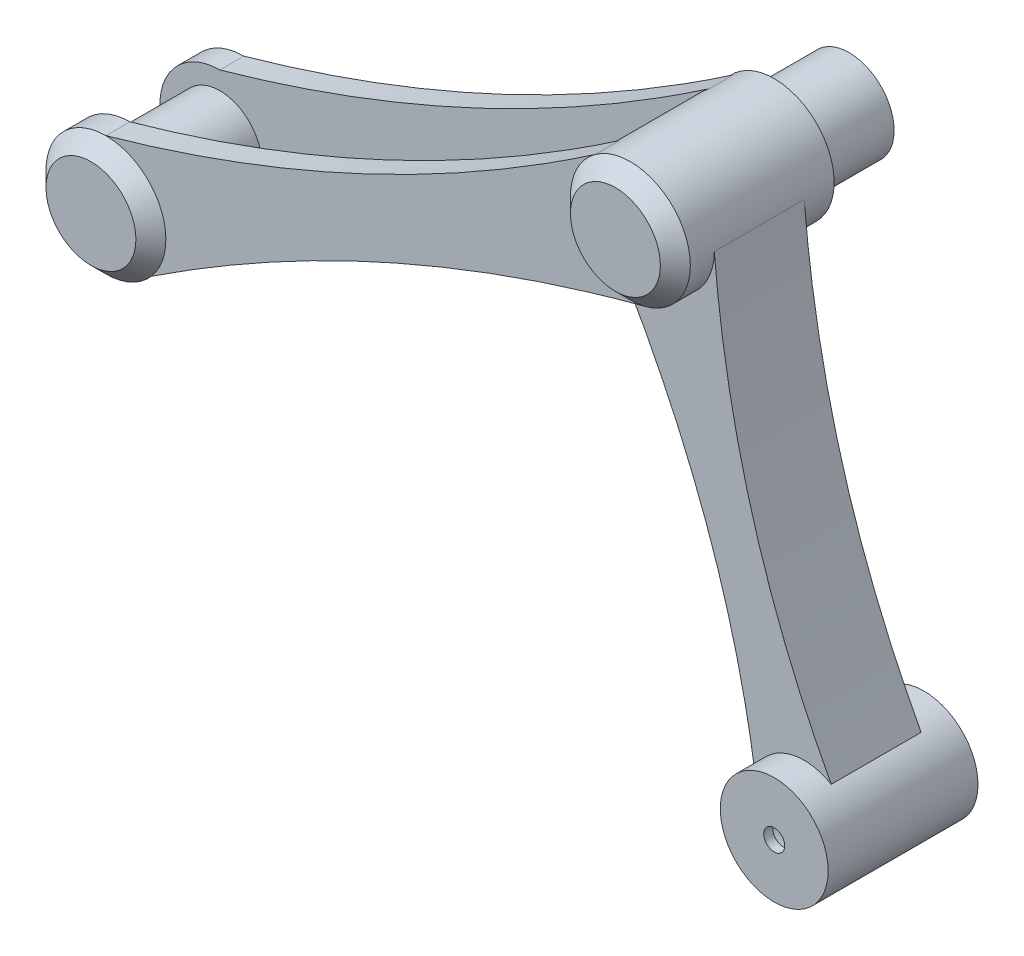
SolidWorks part; units mm, degrees
ref_plane "Front Plane" through (0, 0, 0) normal (0, 0, 1) x (1, 0, 0)
ref_plane "Top Plane" through (0, 0, 0) normal (0, 1, 0) x (1, 0, 0)
ref_plane "Right Plane" through (0, 0, 0) normal (1, 0, 0) x (0, 0, -1)
sketch "Sketch1" plane through (0, 0, 0) normal (0, 0, 1) x (1, 0, 0)
  circle A0 centre (0, 0) radius 14
extrude "Boss-Extrude1" add sketch "Sketch1" against normal blind 15 and the other way blind 15
sketch "Sketch2" plane through (0, 0, 0) normal (0, 0, 1) x (1, 0, 0)
  line L0 (0, 0) -> (175, 0) construction
  line L1 (175, 0) -> (175, 80) construction
  line L2 (175, 0) -> (225, 0) construction
  line L3 (225, 0) -> (225, -70) construction
sketch "Sketch3" plane through (0, 0, -15) normal (0, 0, -1) x (-1, 0, 0)
  circle A0 centre (0, 0) radius 20
extrude "Boss-Extrude2" add sketch "Sketch3" along normal blind 8
sketch "Sketch4" plane through (0, 0, 15) normal (0, 0, 1) x (1, 0, 0)
  circle A0 centre (0, 0) radius 20 construction
  circle A1 centre (0, 0) radius 20
extrude "Boss-Extrude3" add sketch "Sketch4" along normal blind 8
sketch "Sketch6" plane through (0, 0, 0) normal (0, 0, 1) x (1, 0, 0)
  circle A1 centre (175, 80) radius 15
extrude "Boss-Extrude5" add sketch "Sketch6" against normal blind 50 and the other way blind 15 separate body
sketch "Sketch7" plane through (0, 0, 15) normal (0, 0, 1) x (1, 0, 0)
  circle A0 centre (175, 80) radius 20
extrude "Boss-Extrude6" add sketch "Sketch7" along normal blind 10
sketch "Sketch8" plane through (0, 0, -50) normal (0, 0, -1) x (-1, 0, 0)
  line L0 (-182.5, 80) -> (-167.5, 80) construction
  circle A0 centre (-182.5, 80) radius 2
  circle A1 centre (-167.5, 80) radius 2
extrude "Cut-Extrude1" cut sketch "Sketch8" against normal blind 30
sketch "Sketch9" plane through (0, 0, 15) normal (0, 0, -1) x (-1, 0, 0)
  circle A0 centre (-175, 80) radius 15
  circle A1 centre (-175, 80) radius 20
extrude "Boss-Extrude7" add sketch "Sketch9" along normal blind 40
sketch "Sketch10" plane through (0, 0, 25) normal (0, 0, 1) x (1, 0, 0)
  line L0 (0, 0) -> (175, 80) construction
  line L1 (175, 80) -> (225, -70) construction
  circle A0 centre (0, 0) radius 20
  circle A1 centre (175, 80) radius 20
  circle A2 centre (225, -70) radius 18 construction
  circle A3 centre (225, -70) radius 12.8 construction
sketch "Sketch11" plane through (0, 0, 25) normal (0, 0, 1) x (1, 0, 0)
  circle A0 centre (225, -70) radius 18 construction
  circle A1 centre (225, -70) radius 18
  circle A2 centre (225, -70) radius 12.8 construction
  circle A3 centre (225, -70) radius 12.8
sketch "Sketch13" plane through (0, 0, 23) normal (0, 0, 1) x (1, 0, 0)
  line L0 (0, 0) -> (175, 80) construction
  line L1 (175, 80) -> (225, -70) construction
  circle A1 centre (175, 80) radius 20
  circle A2 centre (175, 80) radius 20
  circle A5 centre (0, 0) radius 20
  circle A6 centre (175, 80) radius 20
  spline S0 degree 2 poles (0, 20) (88.2168, 44.7305) (164.022, 96.7178) knots 0 0 0 1 1 1
  spline S1 degree 2 poles (15.1249, -13.0858) (91.5464, 37.447) (180.46, 60.7597) knots 0 0 0 1 1 1
  dimension "D1" = 0
extrude "Boss-Extrude11" add sketch "Sketch13" against normal blind 8 contours A5 S1 A6 S0 region at (88.2976, 40.3646, 23)
mirror "Mirror1" about plane through (0, 0, 0) normal (0, 0, 1) of "Boss-Extrude11"
sketch "Sketch14" plane through (0, 0, 23) normal (0, 0, 1) x (1, 0, 0)
  line L0 (175, 80) -> (225, -70) construction
  arc A0 (159, 68) -> (195, 80) centre (175, 80) ccw
  arc A1 (234.0302, -54.429) -> (208.4333, -62.9613) centre (225, -70) ccw
  spline S0 degree 2 poles (195, 80) (201.2901, 6.2444) (234.0302, -54.429) knots 0 0 0 0.710269 0.710269 0.710269
  spline S1 degree 2 poles (159, 68) (198.2212, 5.2214) (208.4333, -62.9613) knots 0 0 0 0.710269 0.710269 0.710269
sketch "Sketch15" plane through (0, 0, 0) normal (0, 0, 1) x (1, 0, 0)
  circle A0 centre (225, -70) radius 12.8
  circle A1 centre (225, -70) radius 18
extrude "Boss-Extrude12" add sketch "Sketch15" along normal blind 25 and the other way blind 25 separate body
sketch "Sketch16" plane through (0, 0, 25) normal (0, 0, 1) x (1, 0, 0)
  circle A0 centre (225, -70) radius 3.5
  circle A1 centre (225, -70) radius 12.8
extrude "Boss-Extrude13" add sketch "Sketch16" against normal blind 3
ref_plane "Plane1" through (0, 0, 15) normal (0, 0, 1) x (1, 0, 0)
sketch "Sketch17" plane through (0, 0, 15) normal (0, 0, 1) x (1, 0, 0)
  circle A0 centre (225, -70) radius 18 construction
  circle A1 centre (175, 80) radius 20 construction
  arc A2 (234.0302, -54.429) -> (208.4333, -62.9613) centre (225, -70) ccw
  arc A3 (159, 68) -> (195, 80) centre (175, 80) ccw
  parabola Q0 (195, 80) -> (234.0302, -54.429) focus (372.9824, 27.0493) apex (228.7807, -44.2735) construction
  parabola Q1 (159, 68) -> (208.4333, -62.9613) focus (48.3845, -81.15) apex (206.5395, -51.6872) construction
  parabola Q2 (195, 80) -> (234.0302, -54.429) focus (372.9824, 27.0493) apex (228.7807, -44.2735)
  parabola Q3 (159, 68) -> (208.4333, -62.9613) focus (48.3845, -81.15) apex (206.5395, -51.6872)
extrude "Boss-Extrude14" add sketch "Sketch17" against normal blind 30
sketch "Sketch18" plane through (0, 0, -15) normal (0, 0, -1) x (-1, 0, 0)
  line L0 (-175, 80) -> (-225, -70) construction
  arc A0 (-191.133, 68.1794) -> (-169.1859, 60.8637) centre (-175, 80) ccw
  arc A1 (-212.4135, -57.1322) -> (-227.3485, -52.1539) centre (-225, -70) ccw
  spline S0 degree 2 poles (-227.3485, -52.1539) (-200.8356, 6.2714) (-191.133, 68.1794) knots 0 0 0 0.776782 0.776782 0.776782
  spline S1 degree 2 poles (-212.4135, -57.1322) (-198.5687, 5.5158) (-169.1859, 60.8637) knots 0 0 0 0.776782 0.776782 0.776782
extrude "Cut-Extrude2" cut sketch "Sketch18" against normal blind 20
sketch "Sketch19" plane through (0, 0, -15) normal (0, 0, -1) x (-1, 0, 0)
  line L0 (-218.0834, -30.3399) -> (-206.9119, -34.7637)
  line L1 (-195.1238, 46.231) -> (-179.1624, 40.9105)
  parabola Q0 (-191.133, 68.1794) -> (-227.3485, -52.1539) focus (-418.5667, 92.5236) apex (-195.1238, 46.231) construction
  parabola Q1 (-195.1238, 46.231) -> (-218.0834, -30.3399) focus (-418.5667, 92.5236) apex (-195.1238, 46.231)
  parabola Q2 (-212.4135, -57.1322) -> (-169.1859, 60.8637) focus (27.3676, -56.1211) apex (-179.1624, 40.9105) construction
  parabola Q3 (-206.9119, -34.7637) -> (-179.1624, 40.9105) focus (27.3676, -56.1211) apex (-179.1624, 40.9105)
extrude "Boss-Extrude15" add sketch "Sketch19" against normal blind 3
sketch "Sketch20" plane through (0, 0, 23) normal (0, 0, 1) x (1, 0, 0)
  circle A0 centre (0, 0) radius 20 construction
  circle A1 centre (0, 0) radius 20
  circle A2 centre (175, 80) radius 20 construction
  circle A3 centre (175, 80) radius 20
extrude "Boss-Extrude16" add sketch "Sketch20" along normal blind 5
chamfer "Chamfer4" distance 5 angle 45 2 edges at (195, 80, 28) (20, 0, 28)
